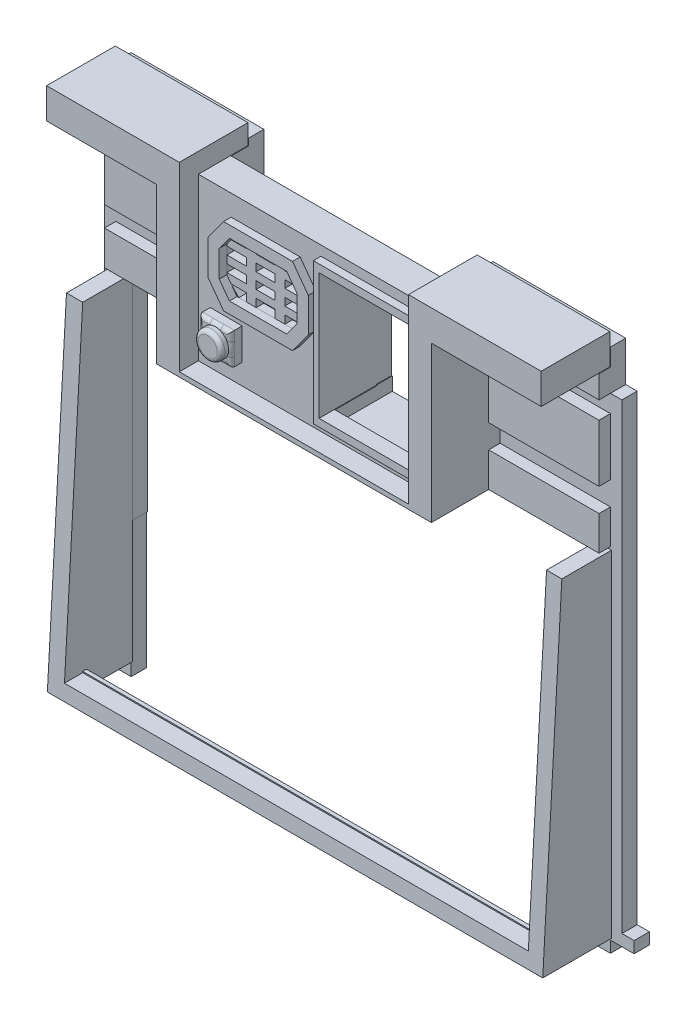
SolidWorks part; units mm, degrees
ref_plane "Front Plane" through (0, 0, 0) normal (0, 0, 1) x (1, 0, 0)
ref_plane "Top Plane" through (0, 0, 0) normal (0, 1, 0) x (1, 0, 0)
ref_plane "Right Plane" through (0, 0, 0) normal (1, 0, 0) x (0, 0, -1)
sketch "Sketch1" plane through (0, 0, 0) normal (0, 0, 1) x (1, 0, 0)
  line L0 (-82.1105, -56.906) -> (-82.1105, -53.906)
  line L1 (-82.1105, -53.906) -> (-85.3105, -53.906)
  line L2 (-85.3105, -53.906) -> (-85.3105, 67.094)
  line L3 (-85.3105, 67.094) -> (-88.3105, 67.094)
  line L4 (-88.3105, 67.094) -> (-88.3105, 77.594)
  line L5 (-88.3105, 77.594) -> (-123.0605, 77.594)
  line L6 (-123.0605, 77.594) -> (-123.0605, 68.844)
  line L7 (-123.0605, 68.844) -> (-124.0605, 68.844)
  line L8 (-124.0605, 68.844) -> (-124.0605, 38.4806)
  line L9 (-124.0605, 38.4806) -> (-152.0605, 38.4806)
  line L10 (-152.0605, 38.4806) -> (-152.0605, 68.844)
  line L11 (-152.0605, 68.844) -> (-155.0605, 68.844)
  line L12 (-155.0605, 68.844) -> (-155.0605, 40.594)
  line L13 (-155.0605, 40.594) -> (-181.0605, 40.594)
  line L14 (-181.0605, 40.594) -> (-181.0605, 68.844)
  line L15 (-181.0605, 68.844) -> (-183.0605, 68.844)
  line L16 (-183.0605, 68.844) -> (-183.0605, 77.594)
  line L17 (-183.0605, 77.594) -> (-217.8105, 77.594)
  line L18 (-217.8105, 77.594) -> (-217.8105, 67.094)
  line L19 (-217.8105, 67.094) -> (-220.8105, 67.094)
  line L20 (-220.8105, 67.094) -> (-220.8105, -53.906)
  line L21 (-220.8105, -53.906) -> (-224.0105, -53.906)
  line L22 (-224.0105, -53.906) -> (-224.0105, -56.906)
  line L23 (-224.0105, -56.906) -> (-217.8105, -56.906)
  line L24 (-217.8105, -56.906) -> (-217.8105, -59.906)
  line L25 (-217.8105, -59.906) -> (-213.8105, -59.906)
  line L26 (-213.8105, -59.906) -> (-213.8105, 31.394)
  line L27 (-213.8105, 31.394) -> (-169.5605, 31.394)
  line L28 (-169.5605, 31.394) -> (-169.5605, 26.094)
  line L29 (-169.5605, 26.094) -> (-136.5605, 26.094)
  line L30 (-136.5605, 26.094) -> (-136.5605, 31.394)
  line L31 (-136.5605, 31.394) -> (-92.3105, 31.394)
  line L32 (-92.3105, 31.394) -> (-92.3105, -59.906)
  line L33 (-92.3105, -59.906) -> (-88.3105, -59.906)
  line L34 (-88.3105, -59.906) -> (-88.3105, -56.906)
  line L35 (-88.3105, -56.906) -> (-82.1105, -56.906)
extrude "Boss-Extrude1" add sketch "Sketch1" along normal blind 4
sketch "Sketch2" plane through (0, 0, 0) normal (0, 0, 1) x (1, 0, 0)
  line L0 (-217.5403, -56.3581) -> (-88.0404, -56.3581)
  line L1 (-217.5403, -56.3581) -> (-88.0404, -56.3581)
  line L2 (-88.0404, -56.3581) -> (-88.0404, 31.6419)
  line L3 (-88.0404, 31.6419) -> (-92.0403, 31.6419)
  line L4 (-92.0403, 31.6419) -> (-92.0403, -52.0576)
  line L5 (-92.0403, -52.0576) -> (-213.5403, -52.0576)
  line L6 (-213.5403, -52.0576) -> (-213.5403, 31.6419)
  line L7 (-213.5403, 31.6419) -> (-217.5403, 31.6419)
  line L8 (-217.5403, 31.6419) -> (-217.5403, -56.3581)
extrude "Boss-Extrude2" add sketch "Sketch2" along normal blind 17 contours L7 L8 L0 L2 L3 L4 L5 L6 region at (-215.9746, -12.3581, 0)
sketch "Sketch3" plane through (0, 0, 0) normal (0, 0, 1) x (1, 0, 0)
  line L42 (-185.5436, 75.8261) -> (-185.5436, 33.2778)
  line L43 (-185.5436, 33.2778) -> (-120.5432, 33.2778)
  line L44 (-120.5432, 33.2778) -> (-120.5432, 75.8261)
  line L45 (-120.5432, 75.8261) -> (-185.5436, 75.8261)
  line L46 (-149.6055, 71.2778) -> (-149.6055, 38.2778)
  line L47 (-149.6055, 38.2778) -> (-125.6055, 38.2778)
  line L48 (-125.6055, 38.2778) -> (-125.6055, 71.2778)
  line L49 (-125.6055, 71.2778) -> (-149.6055, 71.2778)
extrude "Boss-Extrude3" add sketch "Sketch3" along normal blind 17
sketch "Sketch4" plane through (0, 0, 17) normal (0, 0, 1) x (1, 0, 0)
  line L7 (-170.5876, 65.2552) -> (-174.6478, 65.2552)
  line L8 (-170.5876, 65.2552) -> (-170.5876, 67.3858)
  line L9 (-168.0876, 65.2552) -> (-168.0876, 67.3858)
  line L11 (-168.0876, 65.2552) -> (-163.0876, 65.2552)
  line L12 (-163.0876, 65.2552) -> (-163.0876, 67.3858)
  line L13 (-160.5876, 65.2552) -> (-160.5876, 67.3858)
  line L14 (-160.5876, 65.2552) -> (-156.5273, 65.2552)
  line L15 (-160.5876, 63.2552) -> (-155.4225, 63.2552)
  line L16 (-160.5876, 63.2552) -> (-160.5876, 61.2552)
  line L17 (-160.5876, 61.2552) -> (-155.3968, 61.2552)
  line L18 (-160.5876, 59.2552) -> (-155.3711, 59.2552)
  line L19 (-160.5876, 59.2552) -> (-160.5876, 57.2552)
  line L20 (-160.5876, 57.2552) -> (-155.3455, 57.2552)
  line L21 (-160.5876, 55.2552) -> (-156.5273, 55.2552)
  line L22 (-160.5876, 55.2552) -> (-160.5876, 53.1245)
  line L23 (-170.5876, 63.2552) -> (-175.7462, 63.2552)
  line L24 (-170.5876, 63.2552) -> (-170.5876, 61.2552)
  line L25 (-170.5876, 61.2552) -> (-175.7462, 61.2552)
  line L26 (-170.5876, 59.2552) -> (-175.7462, 59.2552)
  line L27 (-170.5876, 59.2552) -> (-170.5876, 57.2552)
  line L28 (-170.5876, 57.2552) -> (-175.7462, 57.2552)
  line L29 (-170.5876, 55.2552) -> (-174.6478, 55.2552)
  line L30 (-170.5876, 55.2552) -> (-170.5876, 53.1245)
  line L31 (-168.0876, 55.2552) -> (-168.0876, 53.1245)
  line L32 (-168.0876, 55.2552) -> (-163.0876, 55.2552)
  line L33 (-163.0876, 55.2552) -> (-163.0876, 53.1245)
  line L34 (-163.0876, 57.2552) -> (-168.0876, 57.2552)
  line L35 (-168.0876, 57.2552) -> (-168.0876, 59.2552)
  line L36 (-168.0876, 59.2552) -> (-163.0876, 59.2552)
  line L37 (-163.0876, 59.2552) -> (-163.0876, 57.2552)
  line L38 (-168.0876, 61.2552) -> (-168.0876, 63.2552)
  line L39 (-168.0876, 63.2552) -> (-163.0876, 63.2552)
  line L40 (-163.0876, 63.2552) -> (-163.0876, 61.2552)
  line L41 (-163.0876, 61.2552) -> (-168.0876, 61.2552)
  line L43 (-155.3711, 59.2552) -> (-155.3455, 57.2552)
  line L44 (-155.4225, 63.2552) -> (-155.3968, 61.2552)
  line L46 (-168.0876, 67.3858) -> (-163.0876, 67.3858)
  line L48 (-175.7462, 63.2552) -> (-175.7462, 61.2552)
  line L49 (-175.7462, 59.2552) -> (-175.7462, 57.2552)
  line L51 (-168.0876, 53.1245) -> (-163.0876, 53.1245)
  line L52 (-160.5876, 53.1245) -> (-158.5574, 53.1245)
  line L53 (-158.5574, 53.1245) -> (-156.5273, 55.2552)
  line L54 (-170.5876, 53.1245) -> (-172.6177, 53.1245)
  line L55 (-172.6177, 53.1245) -> (-174.6478, 55.2552)
  line L56 (-170.5876, 67.3858) -> (-172.6177, 67.3858)
  line L57 (-172.6177, 67.3858) -> (-174.6478, 65.2552)
  line L58 (-160.5876, 67.3858) -> (-158.5574, 67.3858)
  line L59 (-158.5574, 67.3858) -> (-156.5273, 65.2552)
extrude "Cut-Extrude2" cut sketch "Sketch4" against normal blind 26
sketch "Sketch5" plane through (0, 0, 0) normal (0, 0, -1) x (-1, 0, 0)
  line L9 (149.4424, 34.9779) -> (149.4424, 72.0913)
  line L10 (121.4424, 35.2636) -> (149.4424, 34.9779)
  line L11 (121.4424, 72.4694) -> (121.4424, 35.2636)
  line L12 (149.4424, 72.0913) -> (121.4424, 72.4694)
  line L13 (178.4424, 70.0913) -> (152.4424, 70.0913)
  line L14 (178.4424, 37.0913) -> (178.4424, 70.0913)
  line L15 (152.4424, 37.0913) -> (178.4424, 37.0913)
  line L16 (152.4424, 70.0913) -> (152.4424, 37.0913)
extrude "Cut-Extrude3" cut sketch "Sketch5" against normal blind 15
sketch "Sketch7" plane through (0, 75.8261, 0) normal (0, 1, 0) x (1, 0, 0)
  line L1 (-183.0605, 0) -> (-123.0605, 0)
  line L2 (-183.0605, 0) -> (-183.0605, -8.5576)
  line L3 (-183.0605, -8.5576) -> (-123.0605, -8.5576)
  line L4 (-123.0605, 0) -> (-123.0605, -8.5576)
  line L5 (-183.0605, 0) -> (-123.0605, -8.5576) construction
  line L6 (-183.0605, -8.5576) -> (-123.0605, 0) construction
  point P4 (-153.0605, -4.2788)
extrude "Cut-Extrude4" cut sketch "Sketch7" against normal blind 15
sketch "Sketch8" plane through (0, 0, 4) normal (0, 0, 1) x (1, 0, 0)
  line L0 (-217.9528, 73.0289) -> (-217.9528, 81.0289)
  line L1 (-217.9528, 81.0289) -> (-183.2028, 81.0289)
  line L2 (-183.2028, 81.0289) -> (-183.2028, 33.5289)
  line L3 (-183.2028, 33.5289) -> (-123.2028, 33.5289)
  line L4 (-123.2028, 33.5289) -> (-123.2028, 81.0289)
  line L5 (-123.2028, 81.0289) -> (-88.4528, 81.0289)
  line L6 (-88.4528, 81.0289) -> (-88.4528, 73.0289)
  line L7 (-88.4528, 73.0289) -> (-117.2028, 73.0289)
  line L8 (-117.2028, 73.0289) -> (-117.2028, 32.3289)
  line L9 (-117.2028, 32.3289) -> (-189.2028, 32.3289)
  line L10 (-189.2028, 32.3289) -> (-189.2028, 73.0289)
  line L11 (-189.2028, 73.0289) -> (-217.9528, 73.0289)
extrude "Boss-Extrude4" add sketch "Sketch8" along normal blind 18
sketch "Sketch10" plane through (0, 0, 17) normal (0, 0, 1) x (1, 0, 0)
  line L1 (-149.6055, 71.2778) -> (-125.6055, 71.2778)
  line L2 (-149.6055, 71.2778) -> (-149.6055, 38.2778)
  line L3 (-149.6055, 38.2778) -> (-125.6055, 38.2778)
  line L4 (-125.6055, 71.2778) -> (-125.6055, 38.2778)
  line L5 (-149.6055, 71.2778) -> (-125.6055, 38.2778) construction
  line L6 (-149.6055, 38.2778) -> (-125.6055, 71.2778) construction
  line L7 (-151.1055, 36.2778) -> (-124.1055, 36.2778)
  line L8 (-151.1055, 36.2778) -> (-151.1055, 73.2778)
  line L9 (-151.1055, 73.2778) -> (-124.1055, 73.2778)
  line L10 (-124.1055, 36.2778) -> (-124.1055, 73.2778)
  line L11 (-151.1055, 36.2778) -> (-124.1055, 73.2778) construction
  line L12 (-151.1055, 73.2778) -> (-124.1055, 36.2778) construction
  point P4 (-137.6055, 54.7778)
  point P7 (-137.6055, 54.7778)
  dimension "D1" = 27
  dimension "D2" = 37
extrude "Boss-Extrude5" add sketch "Sketch10" along normal blind 2
sketch "Sketch12" plane through (0, 0, 17) normal (0, 0, 1) x (1, 0, 0)
  line L0 (-175.7483, 63.7552) -> (-175.7483, 56.7691)
  line L1 (-175.7483, 56.7691) -> (-173.0896, 53.1384)
  line L2 (-173.0896, 53.1384) -> (-158.0896, 53.1384)
  line L3 (-158.0896, 53.1384) -> (-155.431, 56.7691)
  line L4 (-155.431, 56.7691) -> (-155.431, 63.7691)
  line L5 (-155.431, 63.7691) -> (-158.0794, 67.3858)
  line L6 (-158.0794, 67.3858) -> (-173.0896, 67.3858)
  line L7 (-173.0896, 67.3858) -> (-175.7483, 63.7552)
  line L8 (-178.7483, 64.7361) -> (-178.7483, 55.7881)
  line L9 (-178.7483, 55.7881) -> (-174.6111, 50.1384)
  line L10 (-174.6111, 50.1384) -> (-156.5681, 50.1384)
  line L11 (-156.5681, 50.1384) -> (-152.431, 55.7881)
  line L12 (-152.431, 55.7881) -> (-152.431, 64.7501)
  line L13 (-152.431, 64.7501) -> (-156.5579, 70.3858)
  line L14 (-156.5579, 70.3858) -> (-174.6111, 70.3858)
  line L15 (-174.6111, 70.3858) -> (-178.7483, 64.7361)
  dimension "D1" = 3
extrude "Boss-Extrude6" add sketch "Sketch12" along normal blind 2
sketch "Sketch13" plane through (0, 0, 17) normal (0, 0, 1) x (1, 0, 0)
  circle A0 centre (-175.7651, 42.9548) radius 3.5
extrude "Boss-Extrude7" add sketch "Sketch13" along normal blind 5
sketch "Sketch15" plane through (0, 0, 17) normal (0, 0, 1) x (1, 0, 0)
  line L1 (-180.0958, 38.8959) -> (-171.749, 38.8959)
  line L2 (-180.0958, 38.8959) -> (-180.0958, 47.1549)
  line L3 (-180.0958, 47.1549) -> (-171.749, 47.1549)
  line L4 (-171.749, 38.8959) -> (-171.749, 47.1549)
  line L5 (-180.0958, 38.8959) -> (-171.749, 47.1549) construction
  line L6 (-180.0958, 47.1549) -> (-171.749, 38.8959) construction
  point P0 (-175.9224, 43.0254)
extrude "Boss-Extrude8" add sketch "Sketch15" along normal blind 3
fillet "Fillet6" radius 1 5 edges at (-171.749, 43.0254, 20) (-175.9224, 38.8959, 20) (-180.0958, 43.0254, 20) (-175.9224, 47.1549, 20) (-172.2651, 42.9548, 22)
sketch "Sketch16" plane through (0, 0, 4) normal (0, 0, 1) x (1, 0, 0)
  line L0 (-117.2028, 67.094) -> (-117.2028, 62.4903) construction
  line L1 (-117.2028, 73.0289) -> (-88.3105, 73.0289)
  line L2 (-117.2028, 73.0289) -> (-117.2028, 67.094)
  line L3 (-117.2028, 67.094) -> (-88.3105, 67.094)
  line L4 (-88.3105, 73.0289) -> (-88.3105, 67.094)
  line L5 (-117.2028, 73.0289) -> (-88.3105, 67.094) construction
  line L6 (-117.2028, 67.094) -> (-88.3105, 73.0289) construction
  line L7 (-117.2028, 32.3289) -> (-117.2028, 73.0289) construction
  line L8 (-189.2028, 67.094) -> (-189.2028, 61.6623) construction
  line L9 (-117.2028, 62.4903) -> (-88.3105, 62.4903)
  line L10 (-117.2028, 62.4903) -> (-117.2028, 47.4903)
  line L11 (-117.2028, 47.4903) -> (-88.3105, 47.4903)
  line L12 (-88.3105, 62.4903) -> (-88.3105, 47.4903)
  line L13 (-117.2028, 62.4903) -> (-88.3105, 47.4903) construction
  line L14 (-117.2028, 47.4903) -> (-88.3105, 62.4903) construction
  line L15 (-117.2028, 32.3289) -> (-88.3105, 32.3289)
  line L16 (-117.2028, 32.3289) -> (-117.2028, 41.3289)
  line L17 (-117.2028, 41.3289) -> (-88.3105, 41.3289)
  line L18 (-88.3105, 32.3289) -> (-88.3105, 41.3289)
  line L19 (-117.2028, 32.3289) -> (-88.3105, 41.3289) construction
  line L20 (-117.2028, 41.3289) -> (-88.3105, 32.3289) construction
  line L25 (-189.2028, 73.0289) -> (-217.8105, 73.0289)
  line L26 (-189.2028, 73.0289) -> (-189.2028, 67.094)
  line L31 (-189.2028, 67.094) -> (-217.8105, 67.094)
  line L32 (-217.8105, 73.0289) -> (-217.8105, 67.094)
  line L37 (-189.2028, 73.0289) -> (-217.8105, 67.094) construction
  line L38 (-189.2028, 67.094) -> (-217.8105, 73.0289) construction
  line L39 (-189.2028, 73.0289) -> (-189.2028, 32.3289) construction
  line L41 (-189.2028, 61.6623) -> (-217.8105, 61.6623)
  line L42 (-189.2028, 61.6623) -> (-189.2028, 46.6623)
  line L43 (-189.2028, 46.6623) -> (-217.8105, 46.6623)
  line L44 (-217.8105, 61.6623) -> (-217.8105, 46.6623)
  line L45 (-189.2028, 61.6623) -> (-217.8105, 46.6623) construction
  line L46 (-189.2028, 46.6623) -> (-217.8105, 61.6623) construction
  line L47 (-189.2028, 32.3289) -> (-217.8105, 32.3289)
  line L48 (-189.2028, 32.3289) -> (-189.2028, 41.3289)
  line L49 (-189.2028, 41.3289) -> (-217.8105, 41.3289)
  line L50 (-217.8105, 32.3289) -> (-217.8105, 41.3289)
  line L51 (-189.2028, 32.3289) -> (-217.8105, 41.3289) construction
  line L52 (-189.2028, 41.3289) -> (-217.8105, 32.3289) construction
  point P4 (-102.7567, 70.0615)
  point P13 (-102.7567, 54.9903)
  point P18 (-102.7567, 36.8289)
  point P24 (-203.5066, 70.0615)
  point P31 (-203.5066, 54.1623)
  point P38 (-203.5066, 36.8289)
  dimension "D1" = 15
  dimension "D2" = 9
  dimension "D3" = 15
  dimension "D4" = 9
extrude "Boss-Extrude9" add sketch "Sketch16" along normal blind 3
ref_plane "Plane1" through (-150, 0, 0) normal (1, 0, 0) x (0, 0, -1)
sketch "Sketch18" plane through (0, -56.3581, 0) normal (0, -1, 0) x (1, 0, 0)
  line L1 (-213.8105, 0) -> (-92.3105, 0)
  line L2 (-213.8105, 0) -> (-213.8105, 16)
  line L3 (-213.8105, 16) -> (-92.3105, 16)
  line L4 (-92.3105, 0) -> (-92.3105, 16)
  line L5 (-213.8105, 0) -> (-92.3105, 16) construction
  line L6 (-213.8105, 16) -> (-92.3105, 0) construction
  point P4 (-153.0605, 8)
  dimension "D1" = 16
extrude "Cut-Extrude5" cut sketch "Sketch18" against normal blind 32
ref_plane "Plane2" through (-92, 0, 0) normal (1, 0, 0) x (0, 0, -1)
ref_plane "Plane3" through (-213.5, 0, 0) normal (1, 0, 0) x (0, 0, -1)
sketch "Sketch21" plane through (-213.5, 0, 0) normal (1, 0, 0) x (0, 0, -1)
  line L0 (-17, -56.3581) -> (-22, -56.3581)
  line L1 (-22, -56.3581) -> (-17, 31.6419)
  line L2 (-17, 31.6419) -> (-4, 31.6419)
  line L3 (-4, 67.094) -> (-4, -53.906) construction
  line L4 (-4, 31.6419) -> (-4, -56.3581)
  line L5 (-4, -56.3581) -> (-17, -56.3581)
extrude "Boss-Extrude11" add sketch "Sketch21" against normal blind 4.25
sketch "Sketch22" plane through (-88.0404, 0, 0) normal (1, 0, 0) x (0, 0, -1)
  line L0 (-17, 31.6419) -> (-22, -56.3581)
  line L1 (-22, -56.3581) -> (-4, -56.3581)
  line L2 (-4, -56.3581) -> (-4, 31.6419)
  line L3 (-4, 31.6419) -> (-17, 31.6419)
extrude "Boss-Extrude12" add sketch "Sketch22" against normal blind 4
sketch "Sketch24" plane through (-213.5, 0, 0) normal (1, 0, 0) x (0, 0, -1)
  line L0 (-22, -56.3581) -> (-17, -56.3581)
  line L1 (-22, -56.3581) -> (-4, -56.3581) construction
  line L2 (-17, -56.3581) -> (-17, -52.3581)
  line L3 (-17, -52.3581) -> (-21.7727, -52.3581)
  line L4 (-17, 31.6419) -> (-22, -56.3581) construction
  line L5 (-21.7727, -52.3581) -> (-22, -56.3581)
extrude "Boss-Extrude13" add sketch "Sketch24" along normal blind 124
